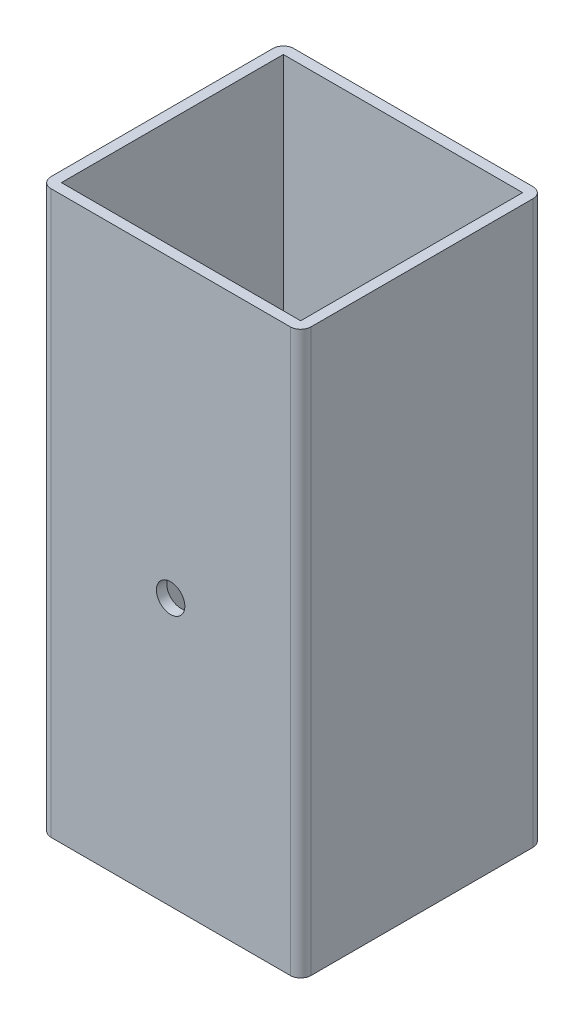
SolidWorks part; units mm, degrees
ref_plane "前视基准面" through (0, 0, 0) normal (0, 0, 1) x (1, 0, 0)
ref_plane "上视基准面" through (0, 0, 0) normal (0, 1, 0) x (1, 0, 0)
ref_plane "右视基准面" through (0, 0, 0) normal (1, 0, 0) x (0, 0, -1)
other "Configuration Table"
sketch "草图1" plane through (0, 0, 0) normal (0, 0, 1) x (1, 0, 0)
  line L0 (0, 0) -> (75, 0)
  line L1 (75, 0) -> (75, 162)
  line L2 (75, 162) -> (0, 162)
  line L3 (0, 162) -> (0, 0)
  dimension "width" = 75
  dimension "height" = 162
extrude "BlockExtrude" add sketch "草图1" along normal blind 70
fillet "Fillet" radius 3 4 edges at (0, 81, 0) (75, 81, 0) (0, 81, 70) (75, 81, 70) tangent propagation no
shell "抽壳1" thickness 3 removed face at (37.5, 162, 35)
sketch "草图2" plane through (0, 0, 0) normal (0, 0, -1) x (-1, 0, 0)
  circle A0 centre (-37.5, 77) radius 4.1
  dimension "diameter" = 8.2
  dimension "x" = 37.5
  dimension "y" = 77
extrude "Cable_entry" cut sketch "草图2" against normal through all
